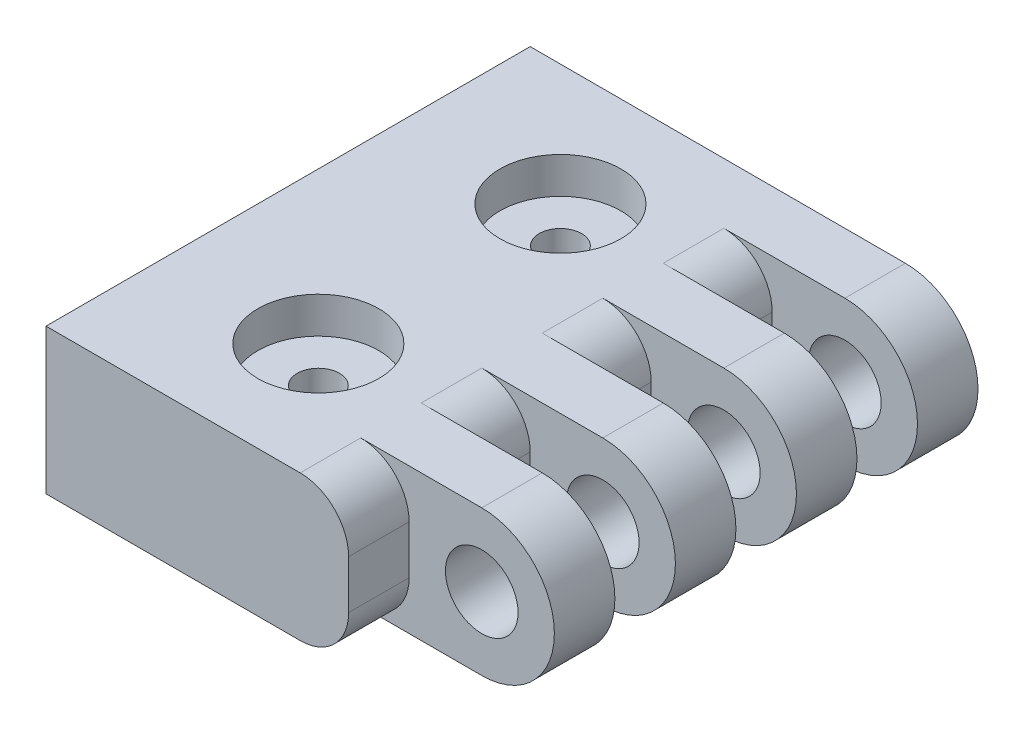
SolidWorks part; units mm, degrees
ref_plane "Front" through (0, 0, 0) normal (0, 0, 1) x (1, 0, 0)
ref_plane "Top" through (0, 0, 0) normal (0, 1, 0) x (1, 0, 0)
ref_plane "Right" through (0, 0, 0) normal (1, 0, 0) x (0, 0, -1)
sketch "Sketch1" plane through (0, 0, 0) normal (0, 1, 0) x (1, 0, 0)
  line L1 (0, 0) -> (-25, 0)
  line L2 (0, 0) -> (0, 40)
  line L3 (0, 40) -> (-25, 40)
  line L4 (-25, 0) -> (-25, 40)
  dimension "D1" = 40
  dimension "D2" = 25
extrude "Boss-Extrude1" add sketch "Sketch1" along normal blind 12
sketch "Sketch2" plane through (0, 0, 0) normal (0, 0, 1) x (1, 0, 0)
  line L0 (0, 0) -> (13.9056, 0) construction
  line L1 (0, 12) -> (0, 0) construction
  line L2 (0, 6) -> (0, 0)
  line L3 (0, 0) -> (6, 0)
  line L4 (0, 6) -> (0, 12)
  line L5 (0, 12) -> (6, 12)
  arc A0 (6, 0) -> (6, 12) centre (6, 6) ccw
  circle A1 centre (6, 6) radius 3
  dimension "D1" = 12
  dimension "D2" = 6
extrude "Boss-Extrude2" add sketch "Sketch2" against normal up to surface (40 mm away) up to face at (-12.5, 6, -40)
sketch "Sketch3" plane through (0, 12, 0) normal (0, 1, 0) x (1, 0, 0)
  line L1 (0, 35) -> (12, 35)
  line L2 (0, 35) -> (0, 30)
  line L3 (0, 30) -> (12, 30)
  line L4 (12, 35) -> (12, 30)
  line L5 (12, 0) -> (12, 40) construction
  line L6 (6, 40) -> (-25, 40) construction
  dimension "D1" = 12
  dimension "D2" = 5
  dimension "7.5" = 5
extrude "Cut-Extrude1" cut sketch "Sketch3" against normal through all
pattern_linear "LPattern1" count 4 spacing 10 along (0, 0, 1) of "Cut-Extrude1"
sketch "Sketch4" plane through (0, 12, 0) normal (0, 1, 0) x (1, 0, 0)
  line L1 (6, 40) -> (-25, 40) construction
  line L2 (-25, 0) -> (0, 0) construction
  line L3 (-12.5, 0) -> (-12.5, 30) construction
  circle A0 centre (-12.5, 30) radius 1.75
  circle A1 centre (-12.5, 10) radius 1.75
  dimension "D4" = 3.5
  dimension "D2" = 10
  dimension "D3" = 10
extrude "Cut-Extrude2" cut sketch "Sketch4" against normal through all
sketch "Sketch5" plane through (0, 12, 0) normal (0, 1, 0) x (1, 0, 0)
  circle A0 centre (-12.5, 30) radius 5
  circle A1 centre (-12.5, 10) radius 5
  dimension "D1" = 10
extrude "Cut-Extrude3" cut sketch "Sketch5" against normal blind 3
pattern_linear "LPattern2" count 2 spacing 9 along (0, -1, 0) of "Cut-Extrude3"
fillet "Fillet1" radius 4 8 edges at (0, 0, -2.5) (0, 12, -2.5) (0, 0, -12.5) (0, 12, -12.5) (0, 0, -22.5) (0, 12, -22.5) (0, 0, -32.5) (0, 12, -32.5)
